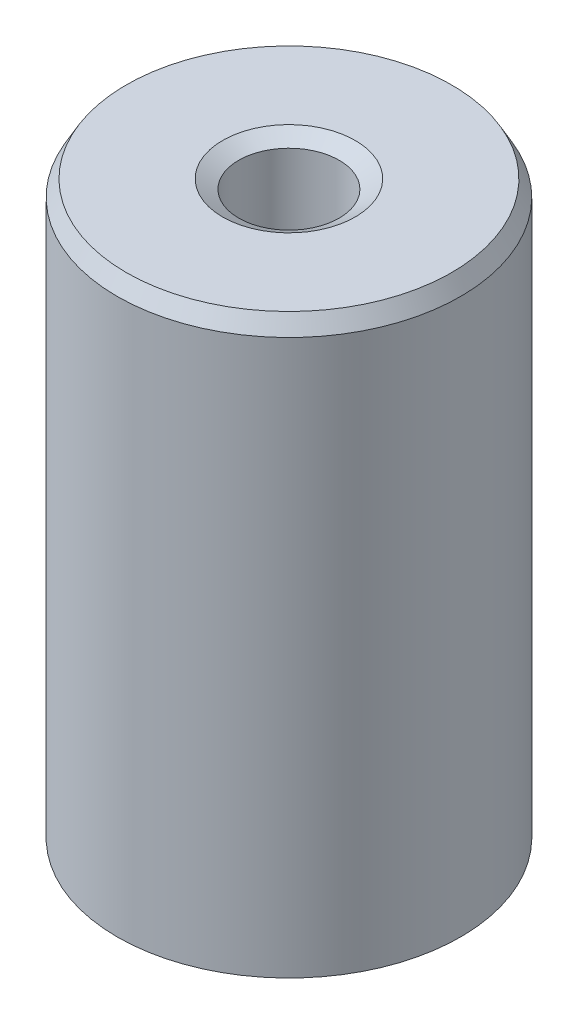
SolidWorks part; units mm, degrees
ref_plane "Front Plane" through (0, 0, 0) normal (0, 0, 1) x (1, 0, 0)
ref_plane "Top Plane" through (0, 0, 0) normal (0, 1, 0) x (1, 0, 0)
ref_plane "Right Plane" through (0, 0, 0) normal (1, 0, 0) x (0, 0, -1)
sketch "Sketch1" plane through (0, 0, 0) normal (0, 1, 0) x (1, 0, 0)
  circle A0 centre (0, 0) radius 5
  dimension "SLEEVE_OD" = 10
extrude "Boss-Extrude1" add sketch "Sketch1" along normal blind 16.8874
sketch "Sketch2" plane through (0, 0, 0) normal (0, 1, 0) x (1, 0, 0)
  circle A0 centre (0, 0) radius 1.4619
  dimension "BORE_D" = 2.9239
extrude "Cut-Extrude1" cut sketch "Sketch2" along normal through all
chamfer "Chamfer1" distance 0.4693 angle 29.356 4 edges at (0, 16.8874, 1.4619) (0, 0, 1.4619) (0, 0, 5) (0, 16.8874, 5) first distance on face at (0, 16.8874, 1.4619) first distance on face at (0, 0, 1.4619) first distance on face at (0, 16.8874, 5)
